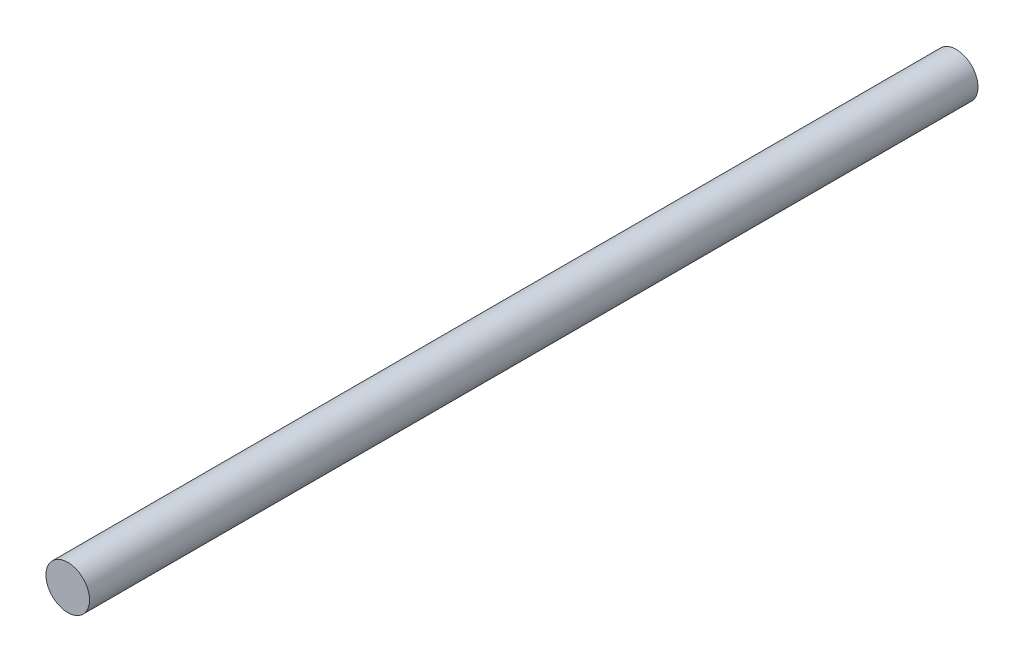
SolidWorks part; units mm, degrees
material "6061-T6 (SS)"
ref_plane "Front Plane" through (0, 0, 0) normal (0, 0, 1) x (1, 0, 0)
ref_plane "Top Plane" through (0, 0, 0) normal (0, 1, 0) x (1, 0, 0)
ref_plane "Right Plane" through (0, 0, 0) normal (1, 0, 0) x (0, 0, -1)
sketch "Sketch1" plane through (0, 0, 0) normal (0, 0, 1) x (1, 0, 0)
  circle A0 centre (0, 0) radius 2.4892
  dimension "D1" = 4.9784
extrude "Boss-Extrude1" add sketch "Sketch1" along normal blind 101.473
